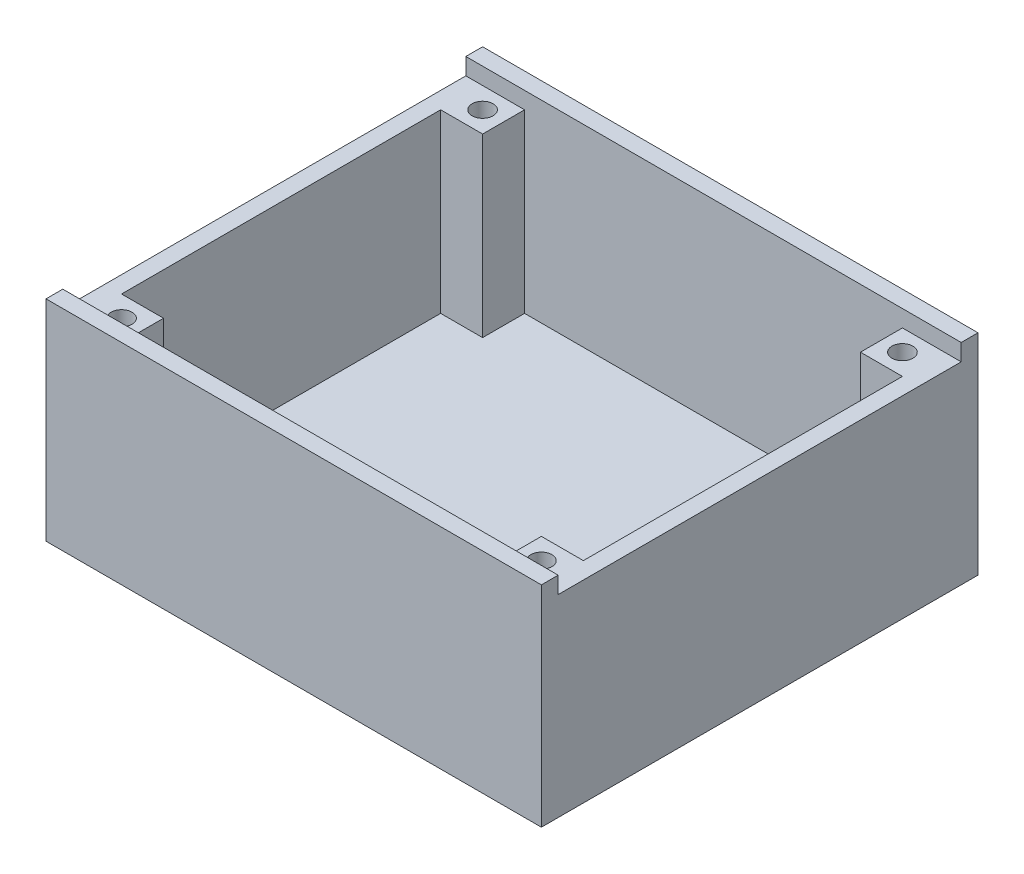
SolidWorks part; units mm, degrees
ref_plane "Front Plane" through (0, 0, 0) normal (0, 0, 1) x (1, 0, 0)
ref_plane "Top Plane" through (0, 0, 0) normal (0, 1, 0) x (1, 0, 0)
ref_plane "Right Plane" through (0, 0, 0) normal (1, 0, 0) x (0, 0, -1)
sketch "Sketch1" plane through (0, 0, 0) normal (0, 1, 0) x (1, 0, 0)
  line L1 (-55, -48) -> (55, -48)
  line L2 (-55, -48) -> (-55, 48)
  line L3 (-55, 48) -> (55, 48)
  line L4 (55, -48) -> (55, 48)
  line L5 (-55, -48) -> (55, 48) construction
  line L6 (-55, 48) -> (55, -48) construction
  line L7 (-59, -52) -> (59, -52)
  line L8 (-59, -52) -> (-59, 52)
  line L9 (-59, 52) -> (59, 52)
  line L10 (59, -52) -> (59, 52)
  line L11 (-59, -52) -> (59, 52) construction
  line L12 (-59, 52) -> (59, -52) construction
  point P0 (0, 0)
  point P6 (0, 0)
  dimension "D1" = 96
  dimension "D2" = 110
  dimension "D3" = 4
  dimension "D4" = 4
extrude "Boss-Extrude1" add sketch "Sketch1" along normal blind 50
extrude "Boss-Extrude2" add sketch "Sketch1<2>" along normal blind 4 contours L8 L9 L10 L7
sketch "Sketch1<2>" plane through (0, 0, 0) normal (0, 1, 0) x (1, 0, 0) same geometry as "Sketch1"
sketch "Sketch2" plane through (59, 0, 0) normal (1, 0, 0) x (0, 0, -1)
  line L0 (-52, 50) -> (52, 50) construction
  line L1 (-48, 50) -> (48, 50)
  line L2 (-48, 50) -> (-48, 46)
  line L3 (-48, 46) -> (48, 46)
  line L4 (48, 50) -> (48, 46)
  line L5 (-48, 50) -> (-48, 4) construction
  line L6 (48, 50) -> (48, 4) construction
  dimension "D1" = 4
extrude "Cut-Extrude1" cut sketch "Sketch2" against normal through all both and the other way through all
sketch "Sketch3" plane through (0, 4, 0) normal (0, 1, 0) x (1, 0, 0)
  line L0 (-27.5, 0) -> (27.5, 0) construction
  line L1 (-55, 48) -> (-45, 48)
  line L2 (-55, 48) -> (-55, 38)
  line L3 (-55, 38) -> (-45, 38)
  line L4 (-45, 48) -> (-45, 38)
  line L5 (-55, -38) -> (-45, -38)
  line L6 (-45, -48) -> (-45, -38)
  line L7 (-55, -48) -> (-45, -48)
  line L8 (-55, -48) -> (-55, -38)
  line L9 (0, -27.5) -> (0, 27.5) construction
  line L10 (55, -48) -> (55, -38)
  line L11 (55, -48) -> (45, -48)
  line L12 (45, -48) -> (45, -38)
  line L13 (55, -38) -> (45, -38)
  line L14 (55, 38) -> (45, 38)
  line L15 (45, 48) -> (45, 38)
  line L16 (55, 48) -> (45, 48)
  line L17 (55, 48) -> (55, 38)
  dimension "D1" = 10
  dimension "D2" = 10
extrude "Boss-Extrude3" add sketch "Sketch3" along normal up to surface (42 mm away) up to face at (-57, 46, 0)
sketch "Sketch4" plane through (0, 46, 0) normal (0, 1, 0) x (1, 0, 0)
  line L0 (-55, 38) -> (-45, 48) construction
  line L1 (0, -27.5) -> (0, 27.5) construction
  line L2 (-27.5, 0) -> (27.5, 0) construction
  circle A0 centre (-50, 43) radius 2.5
  circle A1 centre (50, 43) radius 2.5
  circle A2 centre (50, -43) radius 2.5
  circle A3 centre (-50, -43) radius 2.5
  point P6 (0, 0)
  point P7 (-50, 43)
  dimension "D1" = 5
extrude "Cut-Extrude2" cut sketch "Sketch4" against normal blind 10
